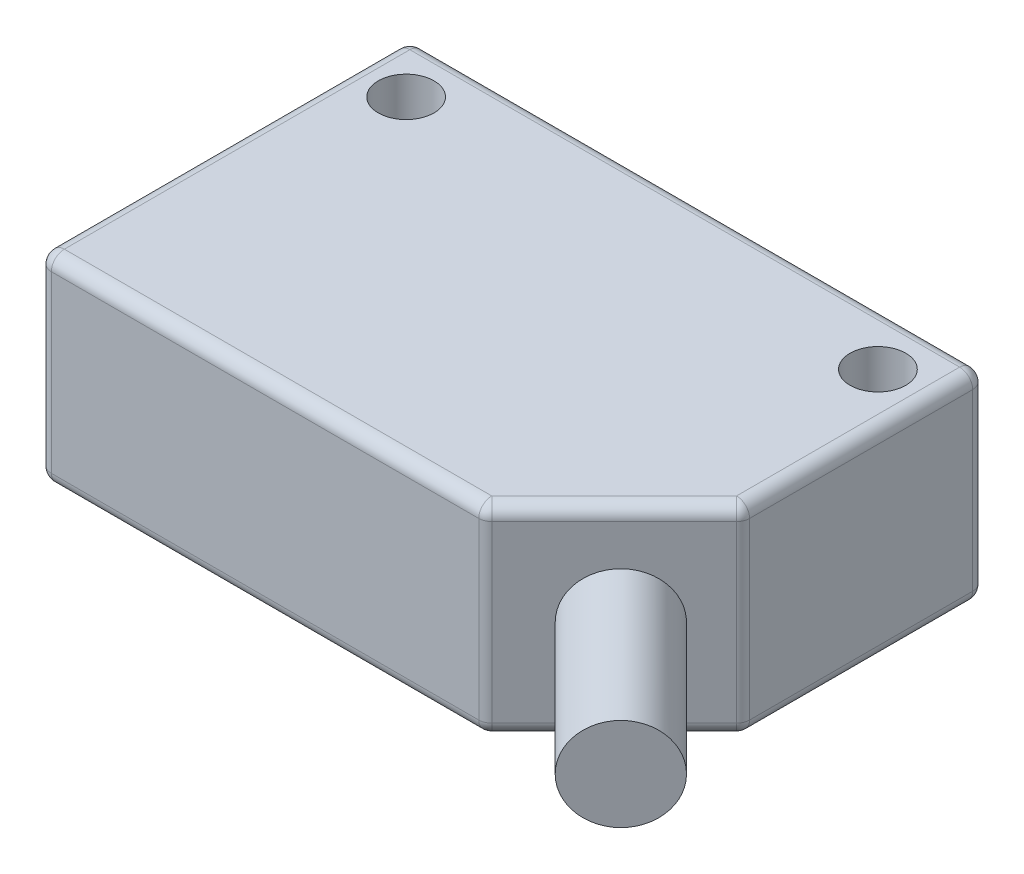
SolidWorks part; units mm, degrees
ref_plane "Front Plane" through (0, 0, 0) normal (0, 0, 1) x (1, 0, 0)
ref_plane "Top Plane" through (0, 0, 0) normal (0, 1, 0) x (1, 0, 0)
ref_plane "Right Plane" through (0, 0, 0) normal (1, 0, 0) x (0, 0, -1)
sketch "Sketch1" plane through (0, 0, 0) normal (0, 1, 0) x (1, 0, 0)
  line L0 (15.5, -3) -> (8.5, -10)
  line L1 (-15.5, -10) -> (8.5, -10)
  line L2 (-15.5, -10) -> (-15.5, 10)
  line L3 (-15.5, 10) -> (15.5, 10)
  line L4 (15.5, -3) -> (15.5, 10)
  line L5 (-15.5, -10) -> (15.5, 10) construction
  line L6 (-15.5, 10) -> (11.2451, -7.2549) construction
  point P0 (0, 0)
  dimension "D1" = 31
extrude "Boss-Extrude1" add sketch "Sketch1" along normal blind 10.8
sketch "Sketch2" plane through (-15.5, 0, 0) normal (-1, 0, 0) x (0, 0, 1)
  line L1 (-10, 10.8) -> (10, 10.8) construction
  line L2 (-1.1538, 9.4) -> (1.3462, 9.4)
  line L3 (-1.1538, 9.4) -> (-1.1538, 1.4)
  line L4 (-1.1538, 1.4) -> (1.3462, 1.4)
  line L5 (1.3462, 9.4) -> (1.3462, 1.4)
  line L6 (-1.1538, 9.4) -> (1.3462, 1.4) construction
  line L7 (-1.1538, 1.4) -> (1.3462, 9.4) construction
  point P2 (0.0962, 5.4)
  dimension "D1" = 2.5
  dimension "D2" = 8
  dimension "D3" = 1.4
extrude "Boss-Extrude2" add sketch "Sketch2" along normal blind 1.2
fillet "Fillet2" radius 1.2 4 edges at (-16.7, 1.4, 0.0962) (-16.7, 5.4, -1.1538) (-16.7, 9.4, 0.0962) (-16.7, 5.4, 1.3462)
fillet "Fillet3" radius 0.5 4 edges at (-16.3485, 9.0485, 0.9947) (-16.3485, 9.0485, -0.8024) (-16.3485, 1.7515, 0.9947) (-16.3485, 1.7515, -0.8024)
fillet "Fillet5" radius 0.3 8 edges at (-15.5, 1.5464, -1.0074) (-15.5, 1.5464, 1.1997) (-15.5, 1.4, 0.0962) (-15.5, 9.2536, -1.0074) (-15.5, 9.2536, 1.1997) (-15.5, 9.4, 0.0962) (-15.5, 5.4, 1.3462) (-15.5, 5.4, -1.1538)
fillet "Fillet7" radius 0.7 15 edges at (8.5, 5.4, 10) (15.5, 5.4, 3) (-3.5, 0, 10) (12, 0, 6.5) (15.5, 0, -3.5) (15.5, 5.4, -10) (0, 0, -10) (-15.5, 5.4, -10) (-15.5, 5.4, 10) (-15.5, 0, 0) (12, 10.8, 6.5) (-3.5, 10.8, 10) (-15.5, 10.8, 0) (0, 10.8, -10) (15.5, 10.8, -3.5)
sketch "Sketch3" plane through (0, 0, -10) normal (0, 0, -1) x (-1, 0, 0)
  line L0 (-14.8, 10.8) -> (14.8, 10.8) construction
  line L1 (-5.5, 1.4) -> (5.5, 1.4)
  line L2 (-5.5, 1.4) -> (-5.5, 9.4)
  line L3 (-5.5, 9.4) -> (5.5, 9.4)
  line L4 (5.5, 1.4) -> (5.5, 9.4)
  line L5 (-5.5, 1.4) -> (5.5, 9.4) construction
  line L6 (-5.5, 9.4) -> (5.5, 1.4) construction
  line L7 (-15.5, 0.7) -> (-15.5, 10.1) construction
  point P0 (0, 5.4)
  dimension "D1" = 8
  dimension "D2" = 11
  dimension "D3" = 1.4
  dimension "D4" = 10
sketch "Sketch4" plane through (9.25, 0, 9.25) normal (0.7071, 0, 0.7071) x (0.7071, 0, -0.7071)
  line L0 (-0.7707, 10.8) -> (8.5489, 10.8) construction
  line L2 (9.0439, 10.1) -> (9.0439, 0.7) construction
  circle A0 centre (4.1439, 5.4) radius 2.5
extrude "Boss-Extrude3" add sketch "Sketch4" along normal blind 10
sketch "Sketch5" plane through (0, 10.8, 0) normal (0, 1, 0) x (1, 0, 0)
  line L0 (-15.5, -9.3) -> (-15.5, 9.3) construction
  line L2 (-14.8, 10) -> (14.8, 10) construction
  circle A0 centre (-12.7, 7) radius 1.5
  dimension "D1" = 2.8
  dimension "D2" = 3
extrude "Cut-Extrude1" cut sketch "Sketch5" against normal blind 10.8
sketch "Sketch6" plane through (0, 10.8, 0) normal (0, 1, 0) x (1, 0, 0)
  line L0 (-14.8, 10) -> (14.8, 10) construction
  line L2 (15.5, 9.3) -> (15.5, -2.7101) construction
  circle A0 centre (12.7, 7) radius 1.5
  dimension "D1" = 3
  dimension "D2" = 2.8
extrude "Cut-Extrude2" cut sketch "Sketch6" against normal blind 10.8
